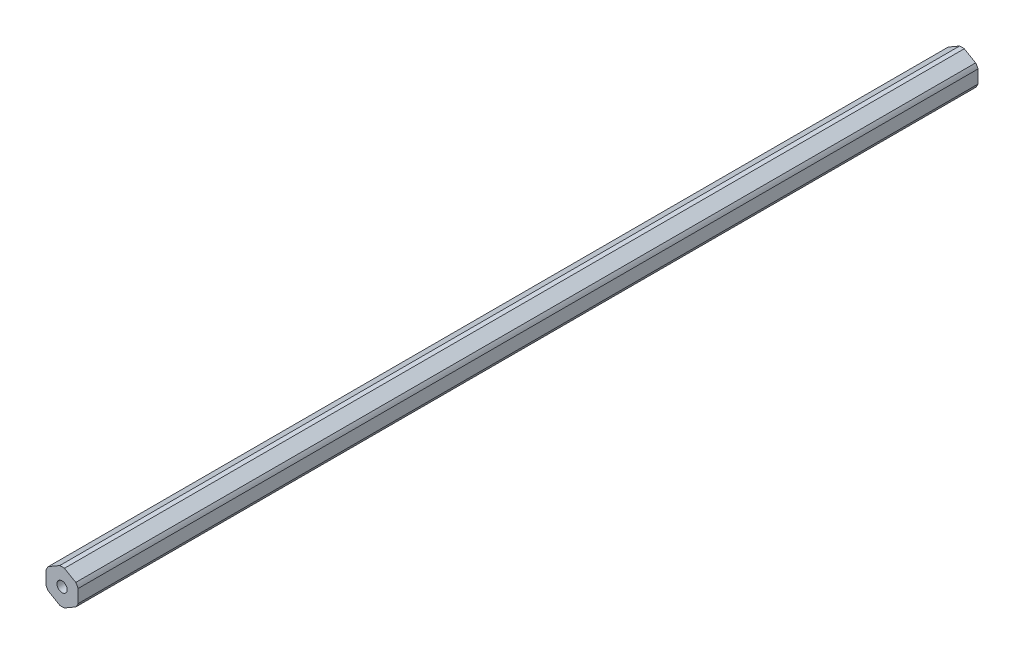
SolidWorks part; units mm, degrees
material "6061-T6 (SS)"
ref_plane "Front Plane" through (0, 0, 0) normal (0, 0, 1) x (1, 0, 0)
ref_plane "Top Plane" through (0, 0, 0) normal (0, 1, 0) x (1, 0, 0)
ref_plane "Right Plane" through (0, 0, 0) normal (1, 0, 0) x (0, 0, -1)
sketch "Sketch1" plane through (0, 0, 0) normal (0, 0, 1) x (1, 0, 0)
  line L1 (0, 7.3323) -> (-6.35, 3.6662)
  line L2 (-6.35, 3.6662) -> (-6.35, -3.6662)
  line L3 (-6.35, -3.6662) -> (0, -7.3323)
  line L4 (0, -7.3323) -> (6.35, -3.6662)
  line L5 (6.35, -3.6662) -> (6.35, 3.6662)
  line L6 (6.35, 3.6662) -> (0, 7.3323)
  circle A0 centre (0, 0) radius 6.35 construction
  circle A1 centre (0, 0) radius 6.858
  dimension "D1" = 12.7
  dimension "D2" = 13.716
extrude "Boss-Extrude1" add sketch "Sketch1" along normal mid plane 355.6 contours L5 A1 L6 L1 L2 L3 L4 region at (0, 0, 0)
sketch "Sketch2" plane through (0, 0, 177.8) normal (0, 0, 1) x (1, 0, 0)
  circle A0 centre (0, 0) radius 2.0193
  dimension "D1" = 4.0386
extrude "Cut-Extrude1" cut sketch "Sketch2" against normal through all
